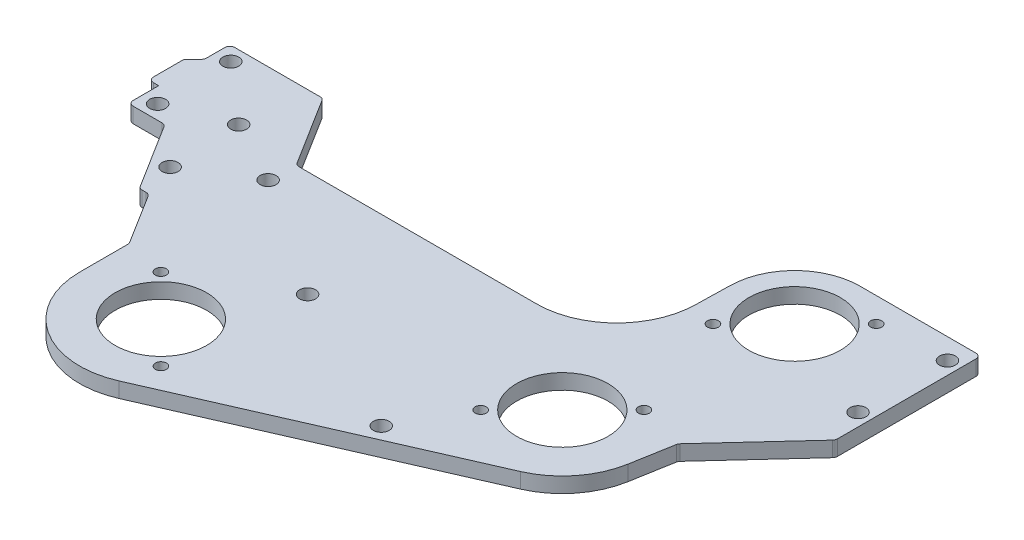
SolidWorks part; units mm, degrees
material "6061 Alloy"
ref_plane "Front Plane" through (0, 0, 0) normal (0, 0, 1) x (1, 0, 0)
ref_plane "Top Plane" through (0, 0, 0) normal (0, 1, 0) x (1, 0, 0)
ref_plane "Right Plane" through (0, 0, 0) normal (1, 0, 0) x (0, 0, -1)
sketch "Sketch1" plane through (0, 0, 0) normal (0, 1, 0) x (1, 0, 0)
  line L1 (-62.0382, -79.8833) -> (25.1671, -41.6958)
  line L5 (39.9402, -22.8907) -> (42.2751, -9.5867)
  line L6 (42.2751, -9.5867) -> (65.831, 16.0128)
  line L16 (-92.7762, 6.1643) -> (-17.7344, 6.1643)
  line L19 (65.831, 61.4936) -> (28.0466, 61.4936)
  line L20 (65.831, 16.0128) -> (65.831, 61.4936)
  line L24 (-218.6325, 207.5765) -> (-97.2237, 13.2819) construction
  line L25 (-106.6713, 28.4011) -> (-92.7762, 6.1643)
  line L26 (-72.2583, -56.6285) -> (15.031, -18.5085) construction
  line L27 (-72.2269, -82.0164) -> (109.3231, -82.0164) construction
  line L28 (15.0167, -18.5164) -> (15.0167, -82.0164) construction
  line L29 (7.3775, 31.2763) -> (7.6, 41.2639)
  line L33 (-110.9585, -24.6526) -> (-138.654, 19.6694) construction
  line L34 (-110.9585, -24.6526) -> (-245.558, 190.7516) construction
  line L36 (-135.7546, 28.4011) -> (-106.6713, 28.4011)
  line L37 (-97.6599, -56.6285) -> (-97.6599, -41.1417)
  line L38 (-107.9634, -24.6526) -> (-97.6599, -41.1417)
  line L40 (-107.9634, -24.6526) -> (-110.9585, -24.6526)
  line L42 (-138.9296, 17.2827) -> (-138.9296, 6.1643)
  line L43 (-92.7762, 6.1643) -> (-138.9296, 6.1643) construction
  line L44 (-138.9296, 6.1643) -> (-135.7546, 6.1643)
  line L45 (-135.7546, 6.1643) -> (-135.7546, -3.3607)
  line L46 (-135.7546, -3.3607) -> (-124.2632, -3.3607)
  line L47 (-124.2632, -3.3607) -> (-110.9585, -24.6526)
  line L48 (-135.7546, 6.1643) -> (-135.7546, 28.4011) construction
  line L49 (-138.9296, 17.2827) -> (-135.7546, 20.4577)
  line L50 (-135.7546, 20.4577) -> (-135.7546, 28.4011)
  circle A0 centre (28.0466, 41.0458) radius 14.29
  circle A1 centre (15.031, -18.5085) radius 14.29
  circle A2 centre (-72.2583, -56.6285) radius 14.29
  arc A4 (39.9402, -22.8907) -> (25.1671, -41.6958) centre (15.0167, -18.5164) cw
  circle A7 centre (15.031, -18.5085) radius 25.4 construction
  circle A8 centre (-72.2583, -56.6285) radius 25.4 construction
  circle A9 centre (-28.6137, -37.5685) radius 22.225 construction
  circle A10 centre (28.0466, 41.0458) radius 30.48 construction
  circle A11 centre (15.031, -18.5085) radius 30.48 construction
  arc A14 (-17.7344, 6.1643) -> (7.3775, 31.2763) centre (-17.7344, 31.2763) ccw
  arc A15 (7.6, 41.2639) -> (28.0466, 61.4936) centre (28.0466, 41.0458) cw
  arc A16 (-62.0382, -79.8833) -> (-97.6599, -56.6285) centre (-72.2583, -56.6285) cw
  point P11 (-62.0382, -79.8833)
  point P34 (15.0167, -18.5164)
  point P35 (28.0466, 41.0458)
  dimension "D2" = 50.8
  dimension "D3" = 50.8
  dimension "D4" = 44.45
  dimension "D5" = 63.5
  dimension "D7" = 60.96
  dimension "D8" = 60.96
  dimension "D1" = 140.0048
  dimension "D6" = 95.25
  dimension "D9" = 50.8
  dimension "D10" = 143.51
extrude "Boss-Extrude1" add sketch "Sketch1" along normal blind 4.7625
hole_wizard "#10 Clearance Hole1" positions "Sketch2" profile "Sketch3" hole size "#10" standard "ANSI Inch" end condition through all
sketch "Sketch2" plane through (0, 4.7625, 0) normal (0, 1, 0) x (1, 0, 0)
  point P0 (61.8305, 55.0158)
  point P3 (61.8305, 27.0758)
  point P7 (-130.9921, 23.9443)
  point P10 (-130.9921, 1.0843)
sketch "Sketch3" plane through (61.8305, 4.7625, -55.0158) normal (1, 0, 0) x (0, 0, 1)
  line L0 (0, 0) -> (0, 4.7625)
  line L1 (0, 4.7625) -> (2.4892, 4.7625)
  line L2 (2.4892, 4.7625) -> (2.4892, 0)
  line L5 (2.4892, 0) -> (0, 0)
  line L11 (0, -6.35) -> (0, 107.95) construction
  dimension "Thru Hole Dia." = 4.9784
  dimension "Thru Hole Depth" = 4.7625
sketch "Sketch4" plane through (0, 4.7625, 0) normal (0, 1, 0) x (1, 0, 0)
  line L0 (-72.2583, -56.6285) -> (-102.5432, -8.1625) construction
  line L1 (-102.5432, -8.1625) -> (-93.1193, -2.2738) construction
  line L2 (-102.5432, -8.1625) -> (-111.9672, -14.0512) construction
  line L3 (-102.5432, -8.1625) -> (-112.7324, 8.1436) construction
  line L4 (-102.5432, -8.1625) -> (-174.2713, 106.6264) construction
  line L5 (65.831, 41.0458) -> (65.831, 28.3458) construction
  dimension "D1" = 57.15
  dimension "D2" = 22.225
  dimension "D3" = 32
hole_wizard "#10 Clearance Hole2" positions "Sketch5" profile "Sketch6" hole size "#10" standard "ANSI Inch" end condition through all
sketch "Sketch5" plane through (0, 4.7625, 0) normal (0, 1, 0) x (1, 0, 0)
  point P0 (-111.9672, -14.0512)
  point P3 (-93.1193, -2.2738)
  point P7 (-112.7324, 8.1436)
sketch "Sketch6" plane through (-111.9672, 4.7625, 14.0512) normal (1, 0, 0) x (0, 0, 1)
  line L0 (0, 0) -> (0, 4.7625)
  line L1 (0, 4.7625) -> (2.4892, 4.7625)
  line L2 (2.4892, 4.7625) -> (2.4892, 0)
  line L5 (2.4892, 0) -> (0, 0)
  line L11 (0, -6.35) -> (0, 107.95) construction
  dimension "Thru Hole Dia." = 4.9784
  dimension "Thru Hole Depth" = 4.7625
sketch "Sketch7" plane through (0, 4.7625, 0) normal (0, 1, 0) x (1, 0, 0)
  line L0 (-59.5064, -69.3804) -> (-85.0103, -43.8765) construction
  line L1 (2.279, -31.2604) -> (27.783, -5.7565) construction
  line L3 (15.2946, 28.2939) -> (40.7985, 53.7978) construction
  point P7 (-72.2583, -56.6285)
  point P11 (15.031, -18.5085)
  point P13 (28.0466, 41.0458)
hole_wizard "Tap Drill for #8-32 Tap1" positions "Sketch8" profile "Sketch9" hole size "#8-32" standard "ANSI Inch" end condition through all
sketch "Sketch8" plane through (0, 4.7625, 0) normal (0, 1, 0) x (1, 0, 0)
  point P0 (-85.0103, -43.8765)
  point P3 (-59.5064, -69.3804)
  point P6 (2.279, -31.2604)
  point P9 (27.783, -5.7565)
  point P12 (15.2946, 28.2939)
  point P15 (40.7985, 53.7978)
sketch "Sketch9" plane through (-85.0103, 4.7625, 43.8765) normal (1, 0, 0) x (0, 0, 1)
  line L0 (0, 0) -> (0, 4.7625)
  line L1 (0, 4.7625) -> (1.7272, 4.7625)
  line L2 (1.7272, 4.7625) -> (1.7272, 0)
  line L5 (1.7272, 0) -> (0, 0)
  line L11 (0, -6.35) -> (0, 107.95) construction
  dimension "Thru Hole Dia." = 3.4544
  dimension "Thru Hole Depth" = 4.7625
hole_wizard "#10 Clearance Hole3" positions "Sketch11" profile "Sketch12" hole size "#10" standard "ANSI Inch" end condition through all
sketch "Sketch11" plane through (0, 4.7625, 0) normal (0, 1, 0) x (1, 0, 0)
  point P0 (-56.0414, -27.0192)
  point P3 (-8.9513, -51.0906)
sketch "Sketch12" plane through (-56.0414, 4.7625, 27.0192) normal (1, 0, 0) x (0, 0, 1)
  line L0 (0, 0) -> (0, 4.7625)
  line L1 (0, 4.7625) -> (2.4892, 4.7625)
  line L2 (2.4892, 4.7625) -> (2.4892, 0)
  line L5 (2.4892, 0) -> (0, 0)
  line L11 (0, -6.35) -> (0, 107.95) construction
  dimension "Thru Hole Dia." = 4.9784
  dimension "Thru Hole Depth" = 4.7625
fillet "Fillet1" radius 1.5875 14 edges at (-135.7546, 2.3813, 3.3607) (-124.2632, 2.3813, 3.3607) (65.831, 2.3813, -61.4936) (65.831, 2.3813, -16.0128) (42.2751, 2.3813, 9.5867) (-97.6599, 2.3813, 41.1417) (-92.7762, 2.3813, -6.1643) (-106.6713, 2.3813, -28.4011) (-138.9296, 2.3813, -17.2827) (-107.9634, 2.3813, 24.6526) (-110.9585, 2.3813, 24.6526) (-135.7546, 2.3813, -28.4011) (-135.7546, 2.3813, -20.4577) (-138.9296, 2.3813, -6.1643)
